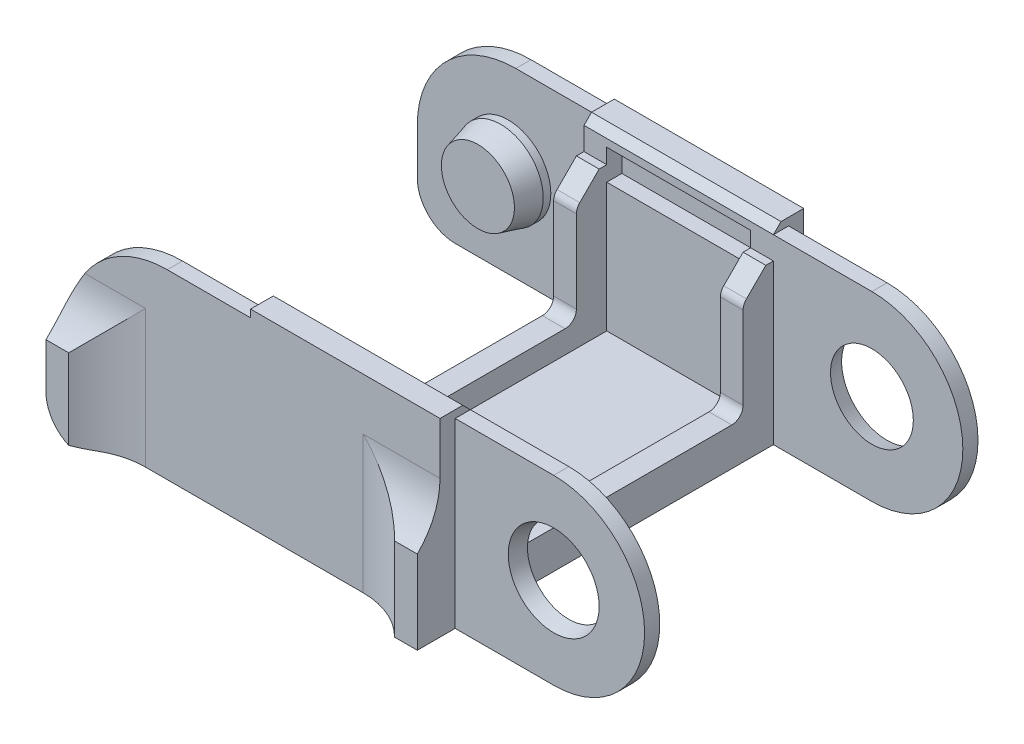
SolidWorks part; units mm, degrees
ref_plane "Front" through (0, 0, 0) normal (0, 0, 1) x (1, 0, 0)
ref_plane "Top" through (0, 0, 0) normal (0, 1, 0) x (1, 0, 0)
ref_plane "Right" through (0, 0, 0) normal (1, 0, 0) x (0, 0, -1)
sketch "Эскиз1" plane through (0, 0, 0) normal (0, 0, 1) x (1, 0, 0)
  line L1 (-38.7795, 23.7195) -> (-13.7795, 23.7195)
  line L2 (-38.7795, 23.7195) -> (-38.7795, -1.2805)
  line L3 (-38.7795, -1.2805) -> (-13.7795, -1.2805)
  line L4 (-13.7795, 23.7195) -> (-13.7795, -1.2805)
  dimension "D1" = 25
  dimension "D2" = 25
extrude "Бобышка-Вытянуть1" add sketch "Эскиз1" along normal blind 4
sketch "Эскиз2" plane through (0, 0, 0) normal (0, 0, -1) x (-1, 0, 0)
  line L0 (38.7795, 22.7195) -> (62.7795, 22.7195)
  line L1 (38.7795, 23.7195) -> (38.7795, -1.2805) construction
  line L3 (62.7795, 22.7195) -> (62.7795, -1.2805)
  line L4 (62.7795, -1.2805) -> (38.7795, -1.2805)
  line L5 (38.7795, -1.2805) -> (38.7795, 22.7195)
  dimension "D1" = 24
  dimension "D2" = 24
extrude "Бобышка-Вытянуть2" add sketch "Эскиз2" against normal blind 2
sketch "Эскиз3" plane through (0, 0, 2) normal (0, 0, 1) x (1, 0, 0)
  line L1 (-38.7795, -1.2805) -> (-62.7795, -1.2805) construction
  line L2 (-62.7795, -1.2805) -> (-62.7795, 22.7195) construction
  circle A0 centre (-50.7795, 10.7195) radius 5.625
  dimension "D2" = 11.25
  dimension "D1" = 12
  dimension "D3" = 12
extrude "Бобышка-Вытянуть3" add sketch "Эскиз3" along normal blind 4
chamfer "Фаска1" distance 3 angle 15 1 edges at (-45.1545, 10.7195, 6) first distance on face at (-45.1545, 10.7195, 6)
sketch "Эскиз4" plane through (0, 0, 6) normal (0, 0, 1) x (1, 0, 0)
  circle A1 centre (-50.7795, 10.7195) radius 13
  circle A4 centre (-50.7795, 10.7195) radius 7.5542
sketch "Эскиз5" plane through (0, 0, 4) normal (0, 0, 1) x (1, 0, 0)
  line L0 (-18.982, 10.7195) -> (-0.7795, 10.7195) construction
  line L1 (-18.982, 22.7195) -> (-0.7795, 22.7195)
  line L2 (-18.982, -1.2805) -> (-0.7795, -1.2805)
  line L3 (-13.7795, -1.2805) -> (-13.7795, 23.7195) construction
  line L4 (-38.7795, -1.2805) -> (-13.7795, -1.2805) construction
  arc A0 (-18.982, 22.7195) -> (-18.982, -1.2805) centre (-18.982, 10.7195) ccw
  arc A1 (-0.7795, -1.2805) -> (-0.7795, 22.7195) centre (-0.7795, 10.7195) ccw
  point P2 (-9.8808, 10.7195)
  dimension "D1" = 13
  dimension "D2" = 12
  dimension "D3" = 12
extrude "Бобышка-Вытянуть4" add sketch "Эскиз5" against normal blind 2
sketch "Эскиз6" plane through (0, 0, 2) normal (0, 0, -1) x (-1, 0, 0)
  circle A0 centre (0.7795, 10.7195) radius 5
  arc A1 (0.7795, 22.7195) -> (0.7795, -1.2805) centre (0.7795, 10.7195) ccw construction
extrude "Вырез-Вытянуть2" cut sketch "Эскиз6" against normal blind 10
sketch "Эскиз8" plane through (0, 0, 4) normal (0, 0, 1) x (1, 0, 0)
  line L5 (-38.7795, 3.7195) -> (-35.7795, 3.7195)
  line L6 (-38.7795, -1.2805) -> (-13.7795, -1.2805)
  line L7 (-38.7795, -1.2805) -> (-38.7795, 3.7195)
  line L9 (-13.7795, -1.2805) -> (-13.7795, 3.7195)
  line L10 (-35.7795, 3.7195) -> (-35.7795, 0.7195)
  line L11 (-35.7795, 0.7195) -> (-16.7795, 0.7195)
  line L12 (-16.7795, 0.7195) -> (-16.7795, 3.7195)
  line L13 (-16.7795, 3.7195) -> (-13.7795, 3.7195)
  line L14 (-13.7795, 22.7195) -> (-13.7795, 23.7195) construction
  dimension "D1" = 3
  dimension "D2" = 3
  dimension "D3" = 2
  dimension "D4" = 5
  dimension "D5" = 5
extrude "Бобышка-Вытянуть6" add sketch "Эскиз8" along normal blind 20
sketch "Эскиз9" plane through (0, 0, 4) normal (0, 0, 1) x (1, 0, 0)
  line L0 (-38.7795, 23.7195) -> (-38.7795, 3.7195) construction
  line L1 (-35.7795, 20.7195) -> (-16.7795, 20.7195)
  line L2 (-35.7795, 20.7195) -> (-35.7795, 17.7195)
  line L3 (-35.7795, 17.7195) -> (-16.7795, 17.7195)
  line L4 (-16.7795, 20.7195) -> (-16.7795, 17.7195)
  line L5 (-13.7795, 22.7195) -> (-13.7795, 23.7195) construction
  line L6 (-13.7795, 23.7195) -> (-38.7795, 23.7195) construction
  dimension "D1" = 3
  dimension "D2" = 3
  dimension "D3" = 3
  dimension "D4" = 6
extrude "Вырез-Вытянуть4" cut sketch "Эскиз9" against normal blind 2
chamfer "Фаска2" distance 1 angle 45 1 edges at (-26.2795, 20.7195, 4)
chamfer "Фаска3" distance 1 angle 75 1 edges at (-5.7795, 10.7195, 2) first distance on face at (-5.7795, 10.7195, 2)
fillet "Скругление1" radius 13 1 edges at (-62.7795, 22.7195, 1)
chamfer "Фаска4" distance 1 angle 45 1 edges at (-26.2795, 23.7195, 4)
sketch "Эскиз11" plane through (0, 3.7195, 0) normal (0, 1, 0) x (1, 0, 0)
  line L0 (-35.7795, -24) -> (-35.7795, -4) construction
  line L1 (-38.7795, -4) -> (-35.7795, -4)
  line L2 (-38.7795, -4) -> (-38.7795, -8)
  line L3 (-38.7795, -8) -> (-35.7795, -8)
  line L4 (-35.7795, -4) -> (-35.7795, -8)
  dimension "D1" = 4
extrude "Бобышка-Вытянуть7" add sketch "Эскиз11" along normal blind 16
pattern_linear "Линейный массив1" count 2 spacing 22 along (1, 0, 0) of "Бобышка-Вытянуть7"
chamfer "Фаска6" distance 3 angle 45 2 edges at (-15.2795, 19.7195, 8) (-37.2795, 19.7195, 8)
fillet "Скругление2" radius 1.5 4 edges at (-15.2795, 3.7195, 8) (-15.2795, 16.7195, 8) (-37.2795, 16.7195, 8) (-37.2795, 3.7195, 8)
sketch "Sketch1" plane through (0, 0, 0) normal (0, 0, -1) x (-1, 0, 0)
  line L0 (62.7795, -1.2805) -> (13.7795, -1.2805) construction
  line L1 (13.7795, 9.7195) -> (16.7795, 9.7195)
  line L2 (13.7795, 9.7195) -> (13.7795, -1.2805)
  line L3 (13.7795, -1.2805) -> (16.7795, -1.2805)
  line L4 (16.7795, 9.7195) -> (16.7795, -1.2805)
  dimension "D1" = 3
  dimension "D2" = 11
extrude "Boss-Extrude1" add sketch "Sketch1" along normal blind 3
fillet "Fillet1" radius 10 2 edges at (-16.7795, 4.2195, 0) (-15.2795, 9.7195, 0)
sketch "Sketch2" plane through (0, 0, 0) normal (0, 0, -1) x (-1, 0, 0)
  line L1 (62.7795, -1.2805) -> (59.7795, -1.2805)
  line L2 (62.7795, -1.2805) -> (62.7795, 9.7195)
  line L3 (62.7795, 9.7195) -> (59.7795, 9.7195)
  line L4 (59.7795, -1.2805) -> (59.7795, 9.7195)
  dimension "D1" = 11
  dimension "D2" = 3
extrude "Boss-Extrude2" add sketch "Sketch2" along normal blind 3
fillet "Fillet2" radius 10 2 edges at (-61.2795, 9.7195, 0) (-59.7795, 4.2195, 0)
fillet "Fillet3" radius 5 1 edges at (-62.7795, -1.2805, -0.5)
mirror "Зеркальное отражение1" about plane through (0, 0, 24) normal (0, 0, -1) of bodies 115 109
